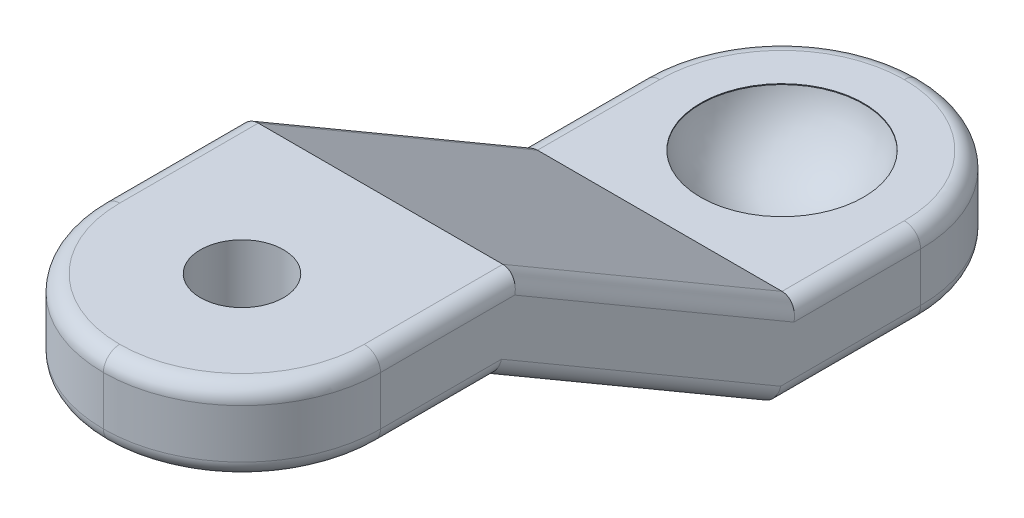
SolidWorks part; units mm, degrees
ref_plane "Front Plane" through (0, 0, 0) normal (0, 0, 1) x (1, 0, 0)
ref_plane "Top Plane" through (0, 0, 0) normal (0, 1, 0) x (1, 0, 0)
ref_plane "Right Plane" through (0, 0, 0) normal (1, 0, 0) x (0, 0, -1)
sketch "ProfileSketch1" plane through (0, 0, 0) normal (1, 0, 0) x (0, 0, -1)
  line L0 (0, 0) -> (34, 0)
  line L1 (34, 0) -> (68.2531, -20)
  line L2 (68.2531, -20) -> (100.2531, -20)
  line L3 (17, 0) -> (17, 2.8642) construction
  line L4 (84.2531, -20) -> (84.2531, 2.8642) construction
  dimension "D1" = 34
  dimension "D2" = 20
  dimension "D4" = 32
  dimension "D3" = 67.2531
extrude "ProfileExtrude-Thin1" add sketch "ProfileSketch1" along normal blind 34 thin thin type one direction wall 10
fillet "Fillet1" radius 17 1 edges at (34, -5, 0)
fillet "Fillet2" radius 17 1 edges at (0, -5, 0)
sketch "FlangeNutHoleSketch4" plane through (0, 0, 0) normal (0, 1, 0) x (1, 0, 0)
  line L0 (0, 17) -> (0, 34) construction
  line L1 (34, 34) -> (0, 34) construction
  circle A0 centre (17, 17) radius 5.1
  dimension "D1" = 17
  dimension "D3" = 10.2
  dimension "D2" = 17
extrude "FlangeNutHoleCut-Extrude5" cut sketch "FlangeNutHoleSketch4" against normal through all
sketch "DomeIndentSketch6" plane through (0, -20, 0) normal (0, 1, 0) x (1, 0, 0)
  line L4 (0, 68.2531) -> (0, 100.2531) construction
  line L5 (34, 100.2531) -> (0, 100.2531) construction
  circle A0 centre (17, 83.2531) radius 10
  dimension "D2" = 17
  dimension "D1" = 20
  dimension "D3" = 17
extrude "DomeIndentCut-Extrude8" cut sketch "DomeIndentSketch6" against normal blind 0.1
dome "Dome2" faces to dome 1 distance 8 reverse direction yes elliptical dome no face at (17, -20.1, -73.2531) parameters "D1"=8
fillet "Fillet3" radius 17 1 edges at (34, -25, -100.2531)
fillet "Fillet4" radius 17 1 edges at (0, -25, -100.2531)
sketch "FlangeNutHolesSketch2" plane through (0, -10, 0) normal (0, -1, 0) x (1, 0, 0)
  line L0 (32, -31.2943) -> (32, -17) construction
  line L1 (34, -31.2943) -> (0, -31.2943) construction
  circle A0 centre (11.3431, -11.3431) radius 2
  circle A1 centre (22.6569, -11.3431) radius 2
  circle A2 centre (22.6569, -22.6569) radius 2
  circle A3 centre (11.3431, -22.6569) radius 2
  point P16 (17, -17)
  dimension "D2" = 4
  dimension "D1" = 8
  dimension "D4" = 8
  dimension "D3" = 4
fillet "BottomBoundaryFillet5" radius 2 10 edges at (0, -20, -48.4208) (0, -30, -74.4003) (4.9792, -30, -95.2739) (29.0208, -30, -95.2739) (34, -30, -74.4003) (34, -20, -48.4208) (34, -10, -24.1471) (29.0208, -10, -4.9792) (4.9792, -10, -4.9792) (0, -10, -24.1471)
fillet "Fillet6" radius 2 10 edges at (34, -10, -51.1266) (34, 0, -25.5) (29.0208, 0, -4.9792) (4.9792, 0, -4.9792) (0, 0, -25.5) (0, -10, -51.1266) (0, -20, -75.7531) (4.9792, -20, -95.2739) (34, -20, -75.7531) (29.0208, -20, -95.2739)
extrude "FlangeNutHolesCut-Extrude1" cut sketch "FlangeNutHolesSketch2" against normal blind 4
equation "\"D1@ProfileSketch1\"=\"BedSupportLeadScrewPadSize\""
equation "\"StandardWallThickness\"= 3mm"
equation "\"BedToBuildPlateStandoffPadSize\"= 10mm"
equation "\"BuildPlateStandoffHolesDistanceFromLeftOrRight\"= 7mm"
equation "\"BuildPlateStandoffHolesDistanceFromFrontOrBack\"= 41mm"
equation "\"DistanceFromBuildPlateSideToStepperHole\"= ( \"DistanceBetweenLeftToRightStepperHoles\" - \"BuildPlateWidth\" ) / 2'Equals 55.825"
equation "\"DistanceBetweenLeftToRightStepperHoles\"= \"FrontBackRailLength\" - \"StepperMountingHoleOffsetFromLeftOrRightSide\" * 2 - \"StepperMountingHoleDistance\"'Equals 461.65"
equation "\"FrontBackRailLength\"= 510mm"
equation "\"StepperMountingHoleOffsetFromLeftOrRightSide\"= \"StepperMountingHoleOffsetFromItsSide\" + \"RailThickness\""
equation "\"StepperMountingHoleDistance\"= 31mm'Spec"
equation "\"StepperMountingHoleOffsetFromItsSide\"= 5.5mm'Spec"
equation "\"RailThickness\"= .125in'Spec"
equation "\"LeadScrewNutPadSize\"= \"LeadScrewNutMountingHoleFlangeDiameter\" + 2mm'Equals 24"
equation "\"LeadScrewNutInnerShaftFlangeDiameter\"= 10.2mm'Spec"
equation "\"LeadScrewNutMountHoleDiameter\"= \"M3HeatInsertHoleDiameter\""
equation "\"LeadScrewNutMountingHoleFlangeDiameter\"= 22mm'Spec"
equation "\"LeadScrewNutMountingHoleDistance\"= 16mm'Spec"
equation "\"M3HeatInsertHoleDiameter\"= 4mm'Spec"
equation "\"D1@Fillet1\"=\"BedSupportLeadScrewPadSize\"/2"
equation "\"D1@Fillet2\"=\"BedSupportLeadScrewPadSize\"/2"
equation "\"D1@FlangeNutHoleSketch4\"=\"BedSupportLeadScrewPadSize\"  / 2"
equation "\"D2@FlangeNutHoleSketch4\"=\"BedSupportLeadScrewPadSize\" / 2"
equation "\"D3@FlangeNutHoleSketch4\" = \"LeadScrewNutInnerShaftFlangeDiameter\""
equation "\"D2@DomeIndentSketch6\" = \"BedSupportLeadScrewPadSize\" / 2"
equation "\"D3@DomeIndentSketch6\" = \"BedSupportLeadScrewPadSize\" / 2"
equation "\"BedSpringHoleSize\"= 3mm"
equation "\"BuildPlateWidth\"= 350mm'Spec"
equation "\"BuildPlateLength\"= 350mm'Spec"
equation "\"BuildPlateBoreDiameter\"= 5mm'Spec"
equation "\"BuildPlateBoreDepth\"= 3mm'Spec"
equation "\"BuildPlateDepth\"= 8mm'Spec"
equation "\"BuildPlateFlankingHoles\"= 38mm"
equation "\"BuildPlateStandoffHolesDistanceFromFront\"= 7mm"
equation "\"BedSupportLeadScrewPadSize\"= \"LeadScrewNutPadSize\" + 10mm"
equation "\"D1@ProfileExtrude-Thin1\"=\"BedSupportLeadScrewPadSize\""
equation "\"BuildPlateBallDiameter\"= 12mm"
equation "\"BedSupportBuildPlatePadSize\"= \"BuildPlateBallDiameter\" + 20mm"
equation "\"D4@ProfileSketch1\"=\"BedSupportBuildPlatePadSize\""
equation "\"D3@ProfileSketch1\" = \"HypotonusOfStepperAndBuildPlateHoles\""
equation "\"D1@Fillet3\"=\"BedSupportLeadScrewPadSize\"/2"
equation "\"D1@Fillet4\"=\"BedSupportLeadScrewPadSize\"/2"
equation "\"HypotonusOfStepperAndBuildPlateHoles\"= sqr ( ( \"DistanceFromBuildPlateSideToStepperHole\" + \"BuildPlateStandoffHolesDistanceFromLeftOrRight\" ) ^ 2 + ( \"BuildPlateStandoffHolesDistanceFromFrontOrBack\" - \"BedSupportLeadScrewPadSize\" / 2 ) ^ 2 )"
equation "\"D1@FlangeNutHolesCut-Extrude1\" = \"M3HeatInsertHoleDiameter\""
equation "\"D1@FlangeNutHolesSketch2\"=\"LeadScrewNutMountingHoleDistance\"/2"
equation "\"D2@FlangeNutHolesSketch2\"=\"M3HeatInsertHoleDiameter\""
equation "\"D4@FlangeNutHolesSketch2\"=\"LeadScrewNutMountingHoleDistance\"/2"
